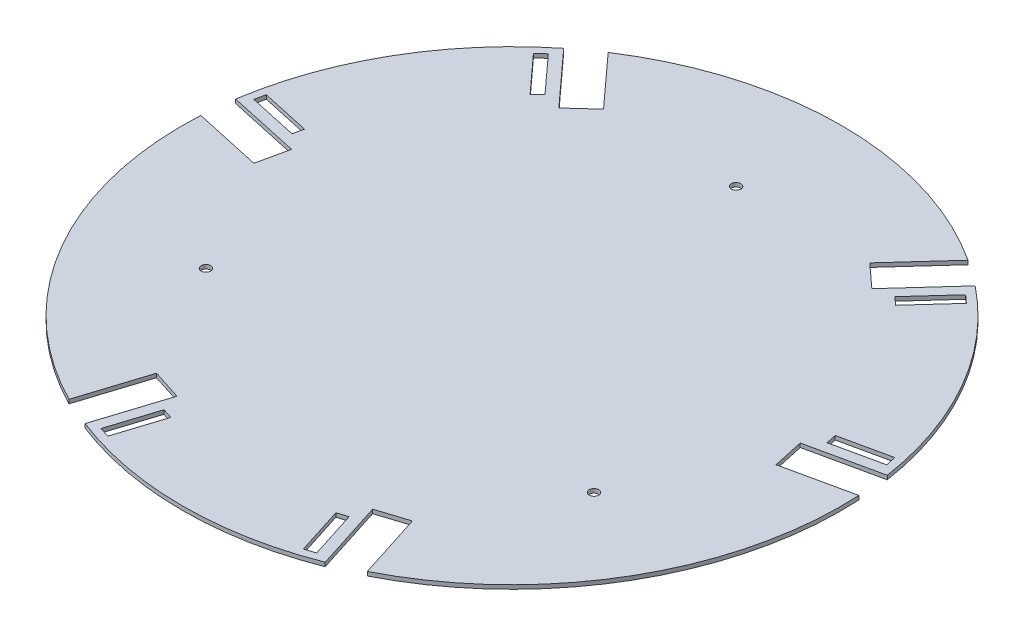
SolidWorks part; units mm, degrees
ref_plane "Front Plane" through (0, 0, 0) normal (0, 0, 1) x (1, 0, 0)
ref_plane "Top Plane" through (0, 0, 0) normal (0, 1, 0) x (1, 0, 0)
ref_plane "Right Plane" through (0, 0, 0) normal (1, 0, 0) x (0, 0, -1)
sketch "Sketch2" plane through (0, 0, 0) normal (0, 1, 0) x (1, 0, 0)
  circle A0 centre (0, 0) radius 125
  dimension "D1" = 250
extrude "Boss-Extrude1" add sketch "Sketch2" along normal blind 1.5 contours A0
sketch "Sketch3" plane through (0, 1.5, 0) normal (0, 1, 0) x (1, 0, 0)
  line L0 (0, 0) -> (-38, -119.084) construction
  line L1 (-270.1917, -358.6733) -> (-267.1917, -358.6733)
  line L2 (-270.1917, -358.6733) -> (-270.1917, -377.6733)
  line L3 (-270.1917, -377.6733) -> (-267.1917, -377.6733)
  line L4 (-267.1917, -358.6733) -> (-267.1917, -377.6733)
  line L9 (-38, -119.084) -> (38, -119.084) construction
  line L10 (0, 0) -> (0, -293.8403) construction
  line L11 (31.312, -98.1252) -> (35.1227, -96.9092)
  line L12 (37.088, -116.226) -> (40.8987, -115.01)
  line L14 (37.088, -116.226) -> (31.312, -98.1252)
  line L15 (40.8987, -115.01) -> (35.1227, -96.9092)
  line L17 (-38, -119.084) -> (-37.088, -116.226) construction
  line L19 (-37.088, -116.226) -> (-31.312, -98.1252)
  line L20 (-37.088, -116.226) -> (-40.8987, -115.01)
  line L21 (-31.312, -98.1252) -> (-35.1227, -96.9092)
  line L22 (-40.8987, -115.01) -> (-35.1227, -96.9092)
  line L52 (-82.1107, 90.2321) -> (-69.3229, 76.1796)
  line L53 (-82.1107, 90.2321) -> (-79.1522, 92.9243)
  line L54 (-79.1522, 92.9243) -> (-66.3645, 78.8717)
  line L55 (-69.3229, 76.1796) -> (-66.3645, 78.8717)
  line L56 (-100.6349, 21.9456) -> (-101.4872, 18.0375)
  line L57 (-120.0509, 22.0857) -> (-101.4872, 18.0375)
  line L58 (-119.1987, 25.9938) -> (-120.0509, 22.0857)
  line L59 (-119.1987, 25.9938) -> (-100.6349, 21.9456)
  line L60 (119.1987, 25.9938) -> (100.6349, 21.9456)
  line L61 (119.1987, 25.9938) -> (120.0509, 22.0857)
  line L62 (120.0509, 22.0857) -> (101.4872, 18.0375)
  line L63 (100.6349, 21.9456) -> (101.4872, 18.0375)
  line L64 (69.3229, 76.1796) -> (66.3645, 78.8717)
  line L65 (79.1522, 92.9243) -> (66.3645, 78.8717)
  line L66 (82.1107, 90.2321) -> (79.1522, 92.9243)
  line L67 (82.1107, 90.2321) -> (69.3229, 76.1796)
  circle A1 centre (0, 0) radius 125 construction
  point P18 (0, 0)
  point P38 (-15.7426, 25.0605)
  point P39 (0, 0)
  point P46 (-7.6333, 12.5317)
  dimension "D1" = 3
  dimension "D2" = 19
  dimension "D3" = 76
  dimension "D4" = 3
  dimension "D5" = 3
  dimension "D7" = 4
  dimension "D8" = 19
extrude "Cut-Extrude1" cut sketch "Sketch3" against normal through all
sketch "Sketch4" plane through (0, 1.5, 0) normal (0, 1, 0) x (1, 0, 0)
  circle A3 centre (0, 85) radius 1.8
  circle A4 centre (73.6122, -42.5) radius 1.8
  circle A5 centre (-73.6122, -42.5) radius 1.8
  point P8 (0, 0)
  dimension "D1" = 85
  dimension "D2" = 3
  dimension "D3" = 3.6
extrude "Cut-Extrude2" cut sketch "Sketch4" against normal through all
sketch "Sketch6" plane through (0, 1.5, 0) normal (0, 1, 0) x (1, 0, 0)
  line L0 (-40.8987, -115.01) -> (-44.7094, -113.794) construction
  line L1 (-35.1227, -96.9092) -> (-40.8987, -115.01) construction
  line L2 (0, 0) -> (0, -140.3527) construction
  line L3 (-44.7094, -113.794) -> (-55.9925, -149.153) construction
  line L4 (-55.9925, -149.153) -> (-67.4246, -145.505)
  line L5 (-55.9925, -149.153) -> (-37.1094, -89.9772)
  line L6 (-67.4246, -145.505) -> (-48.5414, -86.3292)
  line L7 (-37.1094, -89.9772) -> (-48.5414, -86.3292)
  line L8 (67.4246, -145.505) -> (48.5414, -86.3292)
  line L9 (37.1094, -89.9772) -> (48.5414, -86.3292)
  line L10 (55.9925, -149.153) -> (37.1094, -89.9772)
  line L11 (55.9925, -149.153) -> (67.4246, -145.505)
  dimension "D1" = 12
  dimension "D2" = 25
  dimension "D3" = 4
extrude "Cut-Extrude5" cut sketch "Sketch6" against normal through all
pattern_circular "CirPattern2" count 3 over 360 about axis through (0, 1.5, 0) along (0, 1, 0) of "Cut-Extrude5"
